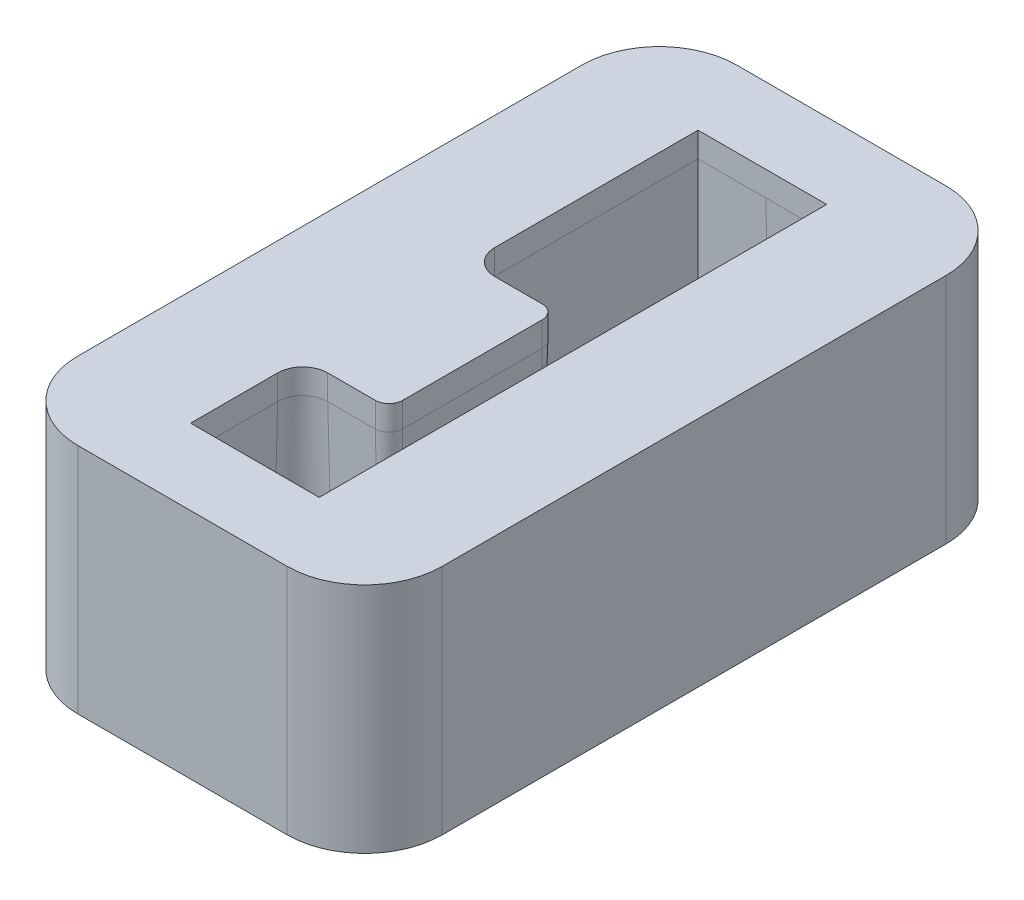
SolidWorks part; units mm, degrees
material "K110"
ref_plane "Front Plane" through (0, 0, 0) normal (0, 0, 1) x (1, 0, 0)
ref_plane "Top Plane" through (0, 0, 0) normal (0, 1, 0) x (1, 0, 0)
ref_plane "Right Plane" through (0, 0, 0) normal (1, 0, 0) x (0, 0, -1)
sketch "Sketch1" plane through (0, 0, 0) normal (0, 1, 0) x (1, 0, 0)
  line L1 (-23.5, -42.5) -> (23.5, -42.5)
  line L2 (-23.5, -42.5) -> (-23.5, 42.5)
  line L3 (-23.5, 42.5) -> (23.5, 42.5)
  line L4 (23.5, -42.5) -> (23.5, 42.5)
  line L5 (-23.5, -42.5) -> (23.5, 42.5) construction
  line L6 (-23.5, 42.5) -> (23.5, -42.5) construction
  point P0 (0, 0)
  dimension "D1" = 85
  dimension "D2" = 47
extrude "Boss-Extrude1" add sketch "Sketch1" against normal blind 30
fillet "Fillet1" radius 10 4 edges at (-23.5, -15, -42.5) (23.5, -15, -42.5) (-23.5, -15, 42.5) (23.5, -15, 42.5)
sketch "Sketch3" plane through (0, 0, 0) normal (0, 1, 0) x (1, 0, 0)
  line L16 (7.86, 32.73) -> (-8.73, 32.73)
  line L17 (-8.73, 32.73) -> (-8.73, 6.5)
  line L18 (-5.5, 3.27) -> (0.63, 3.27)
  line L19 (2.4, 1.5) -> (2.4, -16.5)
  line L20 (0.63, -18.27) -> (-5.5, -18.27)
  line L21 (-8.73, -21.5) -> (-8.73, -32.73)
  line L22 (-8.73, -32.73) -> (7.86, -32.73)
  line L23 (7.86, -32.73) -> (7.86, 32.73)
  line L24 (7.86, 32.73) -> (-8.73, 32.73)
  line L25 (-8.73, 32.73) -> (-8.73, 6.5)
  line L26 (-5.5, 3.27) -> (0.63, 3.27)
  line L27 (2.4, 1.5) -> (2.4, -16.5)
  line L28 (0.63, -18.27) -> (-5.5, -18.27)
  line L29 (-8.73, -21.5) -> (-8.73, -32.73)
  line L30 (-8.73, -32.73) -> (7.86, -32.73)
  line L31 (7.86, -32.73) -> (7.86, 32.73)
  arc A8 (-8.73, 6.5) -> (-5.5, 3.27) centre (-5.5, 6.5) ccw
  arc A9 (2.4, 1.5) -> (0.63, 3.27) centre (0.63, 1.5) ccw
  arc A10 (0.63, -18.27) -> (2.4, -16.5) centre (0.63, -16.5) ccw
  arc A11 (-5.5, -18.27) -> (-8.73, -21.5) centre (-5.5, -21.5) ccw
  arc A12 (-8.73, 6.5) -> (-5.5, 3.27) centre (-5.5, 6.5) ccw
  arc A13 (2.4, 1.5) -> (0.63, 3.27) centre (0.63, 1.5) ccw
  arc A14 (0.63, -18.27) -> (2.4, -16.5) centre (0.63, -16.5) ccw
  arc A15 (-5.5, -18.27) -> (-8.73, -21.5) centre (-5.5, -21.5) ccw
  dimension "D1" = 0.23
extrude "Cut-Extrude1" cut sketch "Sketch3" against normal up to next
sketch "Sketch4" plane through (0, 0, 0) normal (1, 0, 0) x (0, 0, -1)
  line L0 (32.73, -3.2) -> (33.4318, -30)
  line L1 (32.73, -30) -> (32.73, 0) construction
  line L2 (32.5, -30) -> (42.5, -30) construction
  line L3 (33.4318, -30) -> (32.73, -30)
  line L4 (32.73, -30) -> (32.73, -3.2)
  line L5 (25.85, 0) -> (-25.85, 0) construction
  dimension "D1" = 3.2
  dimension "D2" = 1.5
sketch "Sketch5" plane through (0, 0, 0) normal (0, 1, 0) x (1, 0, 0)
  line L0 (-8.73, -32.73) -> (7.86, -32.73) construction
  line L1 (-8.73, -21.5) -> (-8.73, -32.73) construction
  line L2 (0.63, -18.27) -> (-5.5, -18.27) construction
  line L3 (2.4, 1.5) -> (2.4, -16.5) construction
  line L4 (-5.5, 3.27) -> (0.63, 3.27) construction
  line L5 (-8.73, 32.73) -> (-8.73, 6.5) construction
  line L6 (7.86, 32.73) -> (-8.73, 32.73) construction
  line L7 (7.86, -32.73) -> (7.86, 32.73) construction
  line L8 (-8.73, -32.73) -> (7.86, -32.73)
  line L9 (-8.73, -21.5) -> (-8.73, -32.73)
  line L10 (0.63, -18.27) -> (-5.5, -18.27)
  line L11 (2.4, 1.5) -> (2.4, -16.5)
  line L12 (-5.5, 3.27) -> (0.63, 3.27)
  line L13 (-8.73, 32.73) -> (-8.73, 6.5)
  line L14 (7.86, 32.73) -> (-8.73, 32.73)
  line L15 (7.86, -32.73) -> (7.86, 32.73)
  arc A0 (-5.5, -18.27) -> (-8.73, -21.5) centre (-5.5, -21.5) ccw construction
  arc A1 (0.63, -18.27) -> (2.4, -16.5) centre (0.63, -16.5) ccw construction
  arc A2 (2.4, 1.5) -> (0.63, 3.27) centre (0.63, 1.5) ccw construction
  arc A3 (-8.73, 6.5) -> (-5.5, 3.27) centre (-5.5, 6.5) ccw construction
  arc A4 (-5.5, -18.27) -> (-8.73, -21.5) centre (-5.5, -21.5) ccw
  arc A5 (0.63, -18.27) -> (2.4, -16.5) centre (0.63, -16.5) ccw
  arc A6 (2.4, 1.5) -> (0.63, 3.27) centre (0.63, 1.5) ccw
  arc A7 (-8.73, 6.5) -> (-5.5, 3.27) centre (-5.5, 6.5) ccw
sweep "Cut-Sweep1" cut profiles "Sketch4" path "Sketch5"
hole_wizard "M6 Tapped Hole1" positions "Sketch8" profile "Sketch7" tap size "M6" standard "ISO"
sketch "Sketch8" plane through (0, -30, 0) normal (0, -1, 0) x (-1, 0, 0)
  line L0 (-13.5, 42.5) -> (13.5, 42.5) construction
  line L1 (-23.5, -32.5) -> (-23.5, 32.5) construction
  line L2 (23.5, 32.5) -> (23.5, -32.5) construction
  line L3 (13.5, -42.5) -> (-13.5, -42.5) construction
  point P0 (-16.5, 35.5)
  point P2 (16.5, 35.5)
  point P4 (16.5, -35.5)
  point P6 (-16.5, -35.5)
  point P11 (0, 0)
  point P12 (0, 0)
  point P13 (0, 0)
  point P14 (0, 0)
  dimension "D1" = 7
  dimension "D2" = 7
  dimension "D3" = 7
  dimension "D4" = 7
sketch "Sketch7" plane through (16.5, -30, -35.5) normal (1, 0, 0) x (0, 0, -1)
  line L0 (0, 0) -> (0, 18.5022)
  line L1 (0, 18.5022) -> (2.5, 17)
  line L2 (2.5, 17) -> (2.5, 0.525)
  line L3 (2.5, 0.525) -> (3.025, 0)
  line L5 (3.025, 0) -> (0, 0)
  line L6 (-2.5, 0.525) -> (-3.025, 0) construction
  line L10 (0, 18.5022) -> (-2.5, 17) construction
  line L11 (0, -6.35) -> (0, 107.95) construction
  dimension "Tap Drill Dia." = 5
  dimension "Tap Drill Depth" = 17
  dimension "Near C'Sink Dia." = 6.05
  dimension "Near C'Sink Angle" = 90
  dimension "Drill Angle" = 118
cosmetic thread "Hole Thread1"
cosmetic thread "Hole Thread2"
cosmetic thread "Hole Thread3"
cosmetic thread "Hole Thread4"
